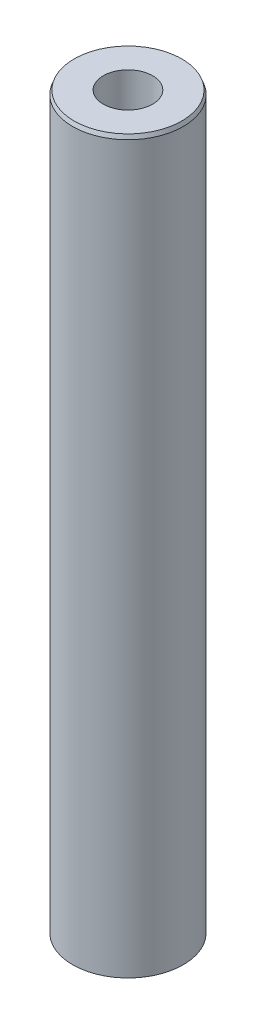
SolidWorks part; units mm, degrees
ref_plane "Front Plane" through (0, 0, 0) normal (0, 0, 1) x (1, 0, 0)
ref_plane "Top Plane" through (0, 0, 0) normal (0, 1, 0) x (1, 0, 0)
ref_plane "Right Plane" through (0, 0, 0) normal (1, 0, 0) x (0, 0, -1)
sketch "Sketch1" plane through (0, 0, 0) normal (0, 1, 0) x (1, 0, 0)
  circle A0 centre (0, 0) radius 12.5
  dimension "SHAFT_OD" = 25
extrude "Boss-Extrude1" add sketch "Sketch1" along normal blind 165.3176
sketch "Sketch2" plane through (0, 0, 0) normal (0, 1, 0) x (1, 0, 0)
  circle A0 centre (0, 0) radius 5.5767
  dimension "BORE_D" = 11.1535
extrude "Cut-Extrude1" cut sketch "Sketch2" along normal through all
chamfer "Chamfer1" distance 0.9132 angle 20.085 2 edges at (0, 165.3176, 12.5) (0, 0, 12.5) first distance on face at (0, 165.3176, 12.5) first distance on face at (0, 0, 5.5767)
